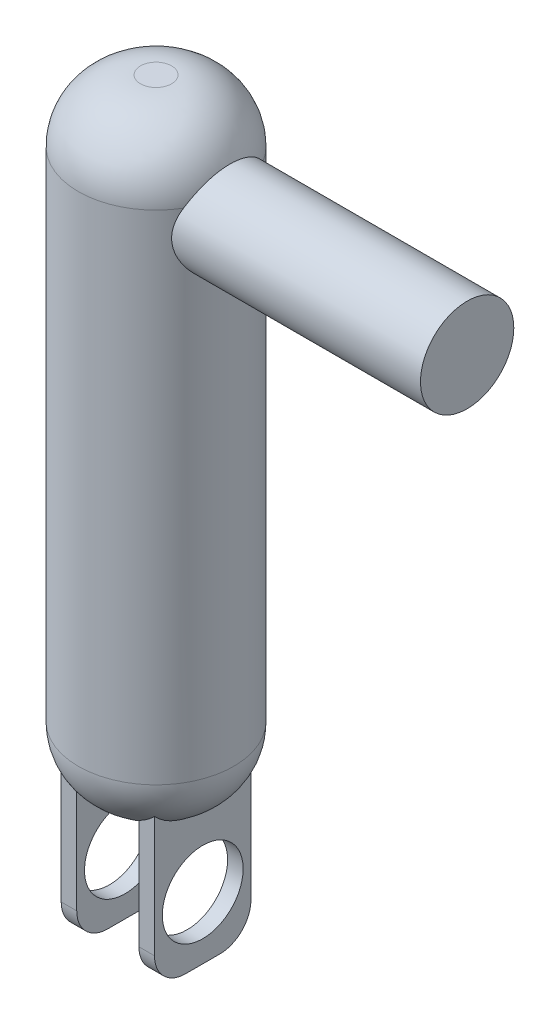
SolidWorks part; units mm, degrees
ref_plane "Front Plane" through (0, 0, 0) normal (0, 0, 1) x (1, 0, 0)
ref_plane "Top Plane" through (0, 0, 0) normal (0, 1, 0) x (1, 0, 0)
ref_plane "Right Plane" through (0, 0, 0) normal (1, 0, 0) x (0, 0, -1)
sketch "Sketch1" plane through (0, 0, 0) normal (0, 1, 0) x (1, 0, 0)
  circle A0 centre (0, 0) radius 2.5
  dimension "D1" = 5
extrude "Boss-Extrude1" add sketch "Sketch1" along normal blind 20
sketch "Sketch3" plane through (0, 0, 0) normal (1, 0, 0) x (0, 0, -1)
  circle A0 centre (0, 17.2021) radius 1.5
extrude "Boss-Extrude3" add sketch "Sketch3" along normal blind 10
sketch "Sketch4" plane through (0, 0, 0) normal (0, -1, 0) x (1, 0, 0)
  line L0 (1, 1.0496) -> (-1, 1.0496)
  line L1 (1.5, 1.5496) -> (-1.5, 1.5496)
  line L2 (1.5, 1.5496) -> (1.5, -1.5496)
  line L3 (1.5, -1.5496) -> (-1.5, -1.5496)
  line L4 (-1.5, 1.5496) -> (-1.5, -1.5496)
  line L5 (1.5, 1.5496) -> (-1.5, -1.5496) construction
  line L6 (1.5, -1.5496) -> (-1.5, 1.5496) construction
  line L7 (-1, 1.0496) -> (-1, -1.0496)
  line L8 (1, -1.0496) -> (-1, -1.0496)
  line L9 (1, 1.0496) -> (1, -1.0496)
  point P0 (0, 0)
  dimension "D1" = 3
  dimension "D2" = 0.5
extrude "Boss-Extrude4" add sketch "Sketch4" along normal blind 4
sketch "Sketch5" plane through (0, -4, 0) normal (0, -1, 0) x (1, 0, 0)
  line L1 (1, 1.6628) -> (-1, 1.6628)
  line L2 (1, 1.6628) -> (1, -1.6628)
  line L3 (1, -1.6628) -> (-1, -1.6628)
  line L4 (-1, 1.6628) -> (-1, -1.6628)
  line L5 (1, 1.6628) -> (-1, -1.6628) construction
  line L6 (1, -1.6628) -> (-1, 1.6628) construction
  point P0 (0, 0)
extrude "Cut-Extrude1" cut sketch "Sketch5" against normal blind 4
sketch "Sketch6" plane through (1.5, 0, 0) normal (1, 0, 0) x (0, 0, -1)
  line L0 (0, -4) -> (0, -2)
  line L1 (1.5496, -4) -> (-1.5496, -4) construction
  circle A0 centre (0, -2) radius 1.3
  dimension "D1" = 2.6
extrude "Cut-Extrude2" cut sketch "Sketch6" against normal blind 4 contours A0 region at (1.5, -2.8932, -0.8932)
fillet "Fillet1" radius 1 4 edges at (-1.25, -4, -1.5496) (1.25, -4, -1.5496) (-1.25, -4, 1.5496) (1.25, -4, 1.5496)
fillet "Fillet2" radius 2 1 edges at (0, 20, 2.5)
fillet "Fillet3" radius 2 1 edges at (0, 0, 2.5)
